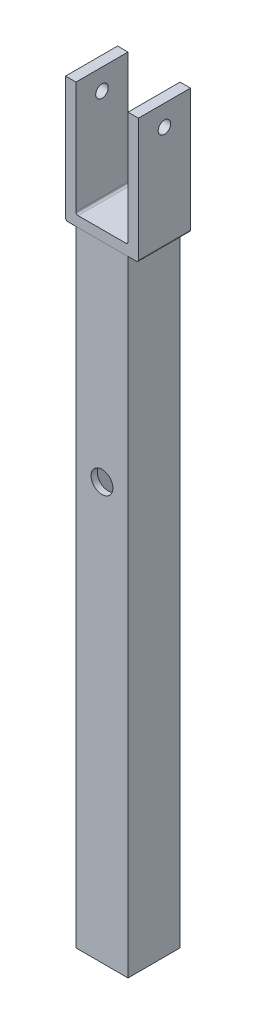
SolidWorks part; units mm, degrees
other "DetailItem2"
other "DetailItem3"
other "Weld Folder"
other "Weld Bead3"
other "Weld Bead2"
ref_plane "Front Plane" through (0, 0, 0) normal (0, 0, 1) x (1, 0, 0)
ref_plane "Top Plane" through (0, 0, 0) normal (0, 1, 0) x (1, 0, 0)
ref_plane "Right Plane" through (0, 0, 0) normal (1, 0, 0) x (0, 0, -1)
sketch "Sketch1" plane through (0, 0, 0) normal (0, 1, 0) x (1, 0, 0)
  line L15 (12.5, 12.5) -> (-12.5, 12.5)
  line L16 (12.5, 12.5) -> (12.5, -12.5)
  line L17 (12.5, -12.5) -> (-12.5, -12.5)
  line L18 (-12.5, 12.5) -> (-12.5, -12.5)
  line L19 (12.5, 12.5) -> (-12.5, -12.5) construction
  line L20 (12.5, -12.5) -> (-12.5, 12.5) construction
  line L21 (-9.5, 9.5) -> (9.5, 9.5)
  line L22 (-9.5, 9.5) -> (-9.5, -9.5)
  line L23 (-9.5, -9.5) -> (9.5, -9.5)
  line L24 (9.5, 9.5) -> (9.5, -9.5)
  line L25 (-9.5, 9.5) -> (9.5, -9.5) construction
  line L26 (-9.5, -9.5) -> (9.5, 9.5) construction
  point P0 (0, 0)
  point P6 (0, 0)
  dimension "D1" = 19
  dimension "D2" = 19
  dimension "D3" = 25
  dimension "D4" = 25
extrude "Boss-Extrude1" add sketch "Sketch1" along normal blind 300
sketch "Sketch2" plane through (0, 0, -12.5) normal (0, 0, -1) x (-1, 0, 0)
  line L0 (0, 0) -> (0, 200)
  line L1 (-12.5, 0) -> (12.5, 0) construction
  circle A0 centre (0, 200) radius 7.5
  dimension "D2" = 15
  dimension "D1" = 200
extrude "Cut-Extrude1" cut sketch "Sketch2" against normal blind 3 contours A0
sketch "Sketch3" plane through (0, 0, 12.5) normal (0, 0, 1) x (1, 0, 0)
  line L0 (0, 0) -> (0, 200)
  line L1 (-12.5, 0) -> (12.5, 0) construction
  circle A0 centre (0, 200) radius 5.25
  dimension "D1" = 10.5
extrude "Cut-Extrude2" cut sketch "Sketch3" against normal blind 3 contours A0
sketch "Sketch5" plane through (0, 300, 0) normal (0, 1, 0) x (1, 0, 0)
  line L1 (17.5, 12.5) -> (-17.5, 12.5)
  line L2 (17.5, 12.5) -> (17.5, -12.5)
  line L3 (17.5, -12.5) -> (-17.5, -12.5)
  line L4 (-17.5, 12.5) -> (-17.5, -12.5)
  line L5 (17.5, 12.5) -> (-17.5, -12.5) construction
  line L6 (17.5, -12.5) -> (-17.5, 12.5) construction
  point P0 (0, 0)
  dimension "D1" = 25
  dimension "D2" = 35
extrude "Boss-Extrude2" add sketch "Sketch5" along normal blind 60 separate body
sketch "Sketch6" plane through (0, 360, 0) normal (0, 1, 0) x (1, 0, 0)
sketch "Sketch7" plane through (0, 360, 0) normal (0, 1, 0) x (1, 0, 0)
  line L0 (17.5, 12.5) -> (-17.5, 12.5) construction
  line L1 (12.5, -12.5) -> (-12.5, -12.5)
  line L2 (12.5, -12.5) -> (12.5, 12.5)
  line L3 (12.5, 12.5) -> (-12.5, 12.5)
  line L4 (-12.5, -12.5) -> (-12.5, 12.5)
  line L5 (12.5, -12.5) -> (-12.5, 12.5) construction
  line L6 (12.5, 12.5) -> (-12.5, -12.5) construction
  point P0 (0, 0)
extrude "Cut-Extrude4" cut sketch "Sketch7" against normal blind 55
sketch "Sketch8" plane through (-17.5, 0, 0) normal (-1, 0, 0) x (0, 0, 1)
  line L0 (0, 360) -> (0, 350)
  line L1 (-12.5, 360) -> (12.5, 360) construction
  circle A0 centre (0, 350) radius 3
  dimension "D2" = 6
  dimension "D1" = 10
extrude "Cut-Extrude5" cut sketch "Sketch8" against normal blind 55 contours A0
fillet "Fillet1" radius 1 2 edges at (12.5, 305, 0) (-12.5, 305, 0)
fillet "Fillet2" radius 1 2 edges at (17.5, 300, 0) (-17.5, 300, 0)
